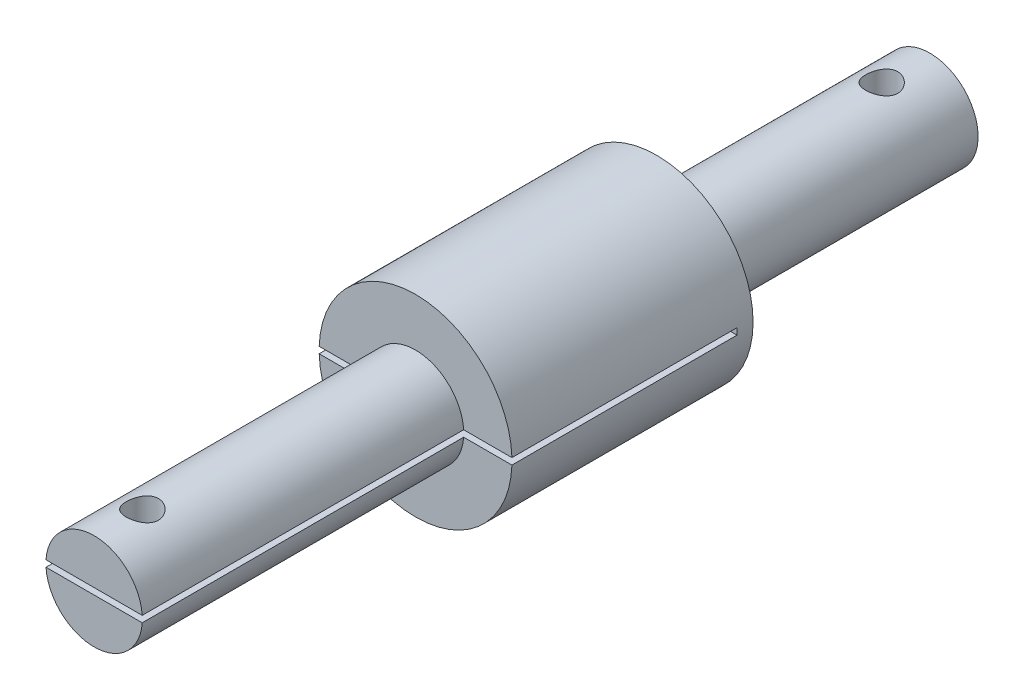
SolidWorks part; units mm, degrees
ref_plane "前视基准面" through (0, 0, 0) normal (0, 0, 1) x (1, 0, 0)
ref_plane "上视基准面" through (0, 0, 0) normal (0, 1, 0) x (1, 0, 0)
ref_plane "右视基准面" through (0, 0, 0) normal (1, 0, 0) x (0, 0, -1)
other "Configuration Table"
sketch "草图1" plane through (0, 0, 0) normal (0, 0, 1) x (1, 0, 0)
  circle A0 centre (0, 0) radius 6
  dimension "D1" = 12
extrude "凸台-拉伸1" add sketch "草图1" along normal blind 15
sketch "草图2" plane through (0, 0, 15) normal (0, 0, 1) x (1, 0, 0)
  circle A0 centre (0, 0) radius 3
  dimension "D1" = 6
extrude "凸台-拉伸2" add sketch "草图2" along normal blind 20
sketch "草图3" plane through (0, 0, 0) normal (0, 0, -1) x (-1, 0, 0)
  circle A0 centre (0, 0) radius 3
  dimension "D1" = 6
extrude "凸台-拉伸3" add sketch "草图3" along normal blind 17
sketch "草图5" plane through (0, 0, 0) normal (0, 1, 0) x (1, 0, 0)
  line L0 (0, -35) -> (0, -36.0365) construction
  line L1 (-3, -35) -> (3, -35) construction
  line L2 (0, 17) -> (0, 9.7003) construction
  line L3 (3, 17) -> (-3, 17) construction
  circle A0 centre (0, -32) radius 1
  circle A1 centre (0, 14) radius 1
  dimension "D1" = 2
  dimension "D3" = 2
  dimension "D2" = 3
  dimension "D4" = 3
extrude "切除-拉伸1" cut sketch "草图5" against normal blind 10 and the other way blind 10
sketch "草图7" plane through (0, 0, 35) normal (0, 0, 1) x (1, 0, 0)
  line L0 (-3, 0) -> (3, 0) construction
  line L2 (-7.4605, 0.2) -> (6.8624, 0.2)
  line L3 (-7.4605, 0.2) -> (-7.4605, -0.2)
  line L4 (-7.4605, -0.2) -> (6.8624, -0.2)
  line L5 (6.8624, 0.2) -> (6.8624, -0.2)
  circle A0 centre (0, 0) radius 3 construction
  circle A1 centre (0, 0) radius 3 construction
  dimension "D1" = 0.4
  dimension "D2" = 0.2
extrude "切除-拉伸2" cut sketch "草图7" against normal blind 34
